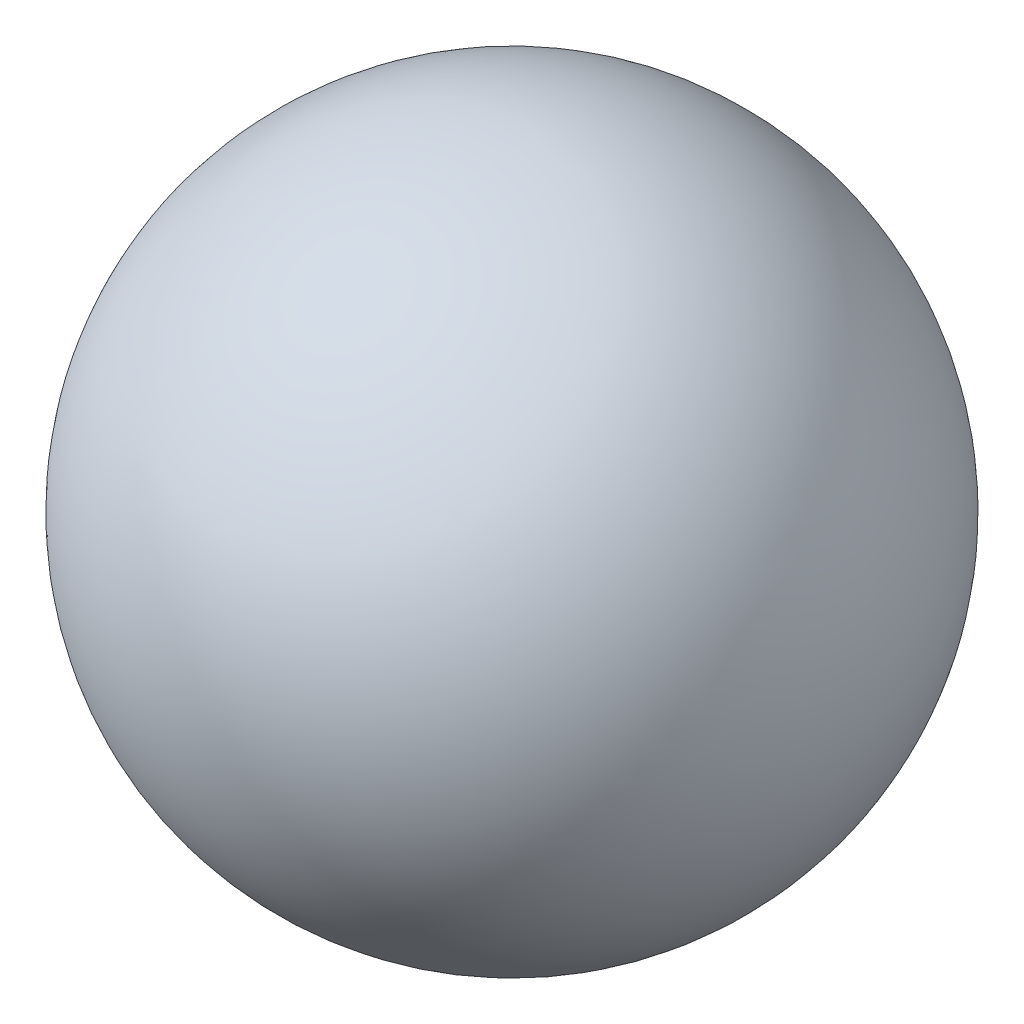
SolidWorks part; units mm, degrees
ref_plane "前基準面" through (0, 0, 0) normal (0, 0, 1) x (1, 0, 0)
ref_plane "上基準面" through (0, 0, 0) normal (0, 1, 0) x (1, 0, 0)
ref_plane "右基準面" through (0, 0, 0) normal (1, 0, 0) x (0, 0, -1)
ref_axis "基準軸1" through (0, -55, 0) along (0, 1, 0)
ref_axis "基準軸2" through (-88.99, 0, 0) along (1, 0, 0)
ref_axis "基準軸3" through (0, 0, 55) along (0, 0, -1)
sketch "草圖1" plane through (0, 0, 0) normal (0, 0, 1) x (1, 0, 0)
  line L0 (-35, 0) -> (35, 0)
  arc A0 (-35, 0) -> (35, 0) centre (0, 0) ccw
  dimension "D1" = 70
revolve "旋轉5" add sketch "草圖1" angle 360 about axis through (-88.99, 0, 0) along (1, 0, 0)
